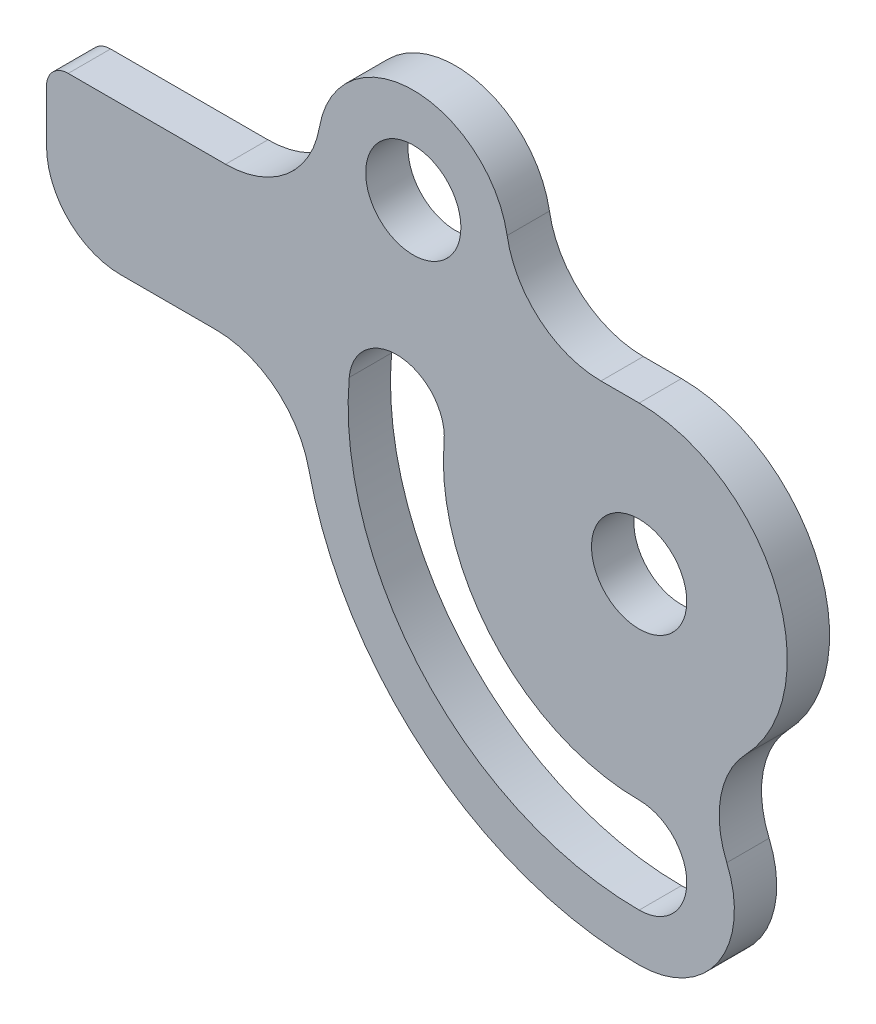
SolidWorks part; units mm, degrees
ref_plane "Front Plane" through (0, 0, 0) normal (0, 0, 1) x (1, 0, 0)
ref_plane "Top Plane" through (0, 0, 0) normal (0, 1, 0) x (1, 0, 0)
ref_plane "Right Plane" through (0, 0, 0) normal (1, 0, 0) x (0, 0, -1)
sketch "Sketch1" plane through (0, 0, 0) normal (0, 0, 1) x (1, 0, 0)
  line L0 (5.5562, 0) -> (16.6687, 0)
  line L1 (0, 5.5562) -> (22.225, 5.5562)
  line L4 (22.225, 5.5562) -> (22.225, -5.5562) construction
  line L5 (0, 5.5562) -> (22.225, 5.5562) construction
  line L9 (13.1316, 0.7956) -> (22.225, 0) construction
  line L10 (22.225, 0) -> (22.225, -9.1281) construction
  line L11 (5.5562, 0) -> (0, 0)
  line L12 (0, 0) -> (0, 5.5562)
  line L13 (13.7542, 7.9121) -> (13.1316, 0.7956) construction
  circle A0 centre (0, 0) radius 5.5562 construction
  circle A1 centre (22.225, 0) radius 5.5562 construction
  circle A2 centre (22.225, -9.1281) radius 3.5719
  arc A3 (22.225, -5.5562) -> (22.225, 5.5562) centre (22.225, 0) ccw
  circle A5 centre (22.225, 0) radius 1.7859
  circle A6 centre (22.225, -9.1281) radius 1.7859
  arc A7 (16.6687, 0) -> (22.225, -5.5562) centre (22.225, 0) ccw
  circle A23 centre (22.225, 0) radius 9.1281 construction
  circle A30 centre (2.7781, 2.7781) radius 2.7781
  circle A31 centre (0.8137, 4.7426) radius 0.8137
  circle A32 centre (13.1316, 0.7956) radius 1.7859
  circle A33 centre (13.1316, 0.7956) radius 3.5719
  circle A34 centre (13.7542, 7.9121) radius 1.7859
  circle A35 centre (13.7542, 7.9121) radius 3.5719
  arc A36 (14.9108, 0.6399) -> (22.225, -7.3422) centre (22.225, 0) ccw
  arc A37 (22.225, -10.9141) -> (11.3525, 0.9512) centre (22.225, 0) cw
  arc A38 (22.225, -12.7) -> (9.5733, 1.1069) centre (22.225, 0) cw
  dimension "D1" = 22.225
  dimension "D2" = 11.1125
  dimension "D3" = 3.5719
  dimension "D5" = 7.1437
  dimension "D4" = 95
extrude "Boss-Extrude1" add sketch "Sketch1" along normal blind 1.5875 contours A38 A2 A37 A33 L0 | A33 A36 A2 A7 L0 | A35 A33 L0 A7 A3 L1 A5 | L0 A37 A32 A36 A33 | L1 A35 | L1 A35 A34 | L0 A38 A33 A35 L1 A30 L11 | A33 A37 L0 | L0 A36 A33 | A38 L0 A33 | A31 A30 | A6 A37 A2 A36 | A30 A31 | A30 A31 | A31 A30 L1 | A31 L12 A30 region at (7.8077, 3.0347, 0) region at (9.5671, 0.2763, 0) region at (14.0442, -7.5172, 0) region at (2.8496, 2.7066, 0) region at (9.6517, 0.5562, 0) region at (10.728, -0.9285, 0) region at (20.2504, -11.9845, 0) region at (0.0964, 3.9168, 0) region at (15.1521, 4.4289, 0) region at (13.7542, 5.062, 0) region at (0.5853, 4.9709, 0) region at (1.0724, 4.4838, 0) region at (1.6395, 5.4598, 0) region at (15.6093, -0.7933, 0) region at (17.7303, -4.1223, 0) region at (12.5283, 11.168, 0)
fillet "Fillet1" radius 3.5719 4 edges at (22.225, -5.5562, 0.7937) (16.439, 5.5562, 0.7937) (11.0694, 5.5562, 0.7937) (9.525, 0, 0.7937)
